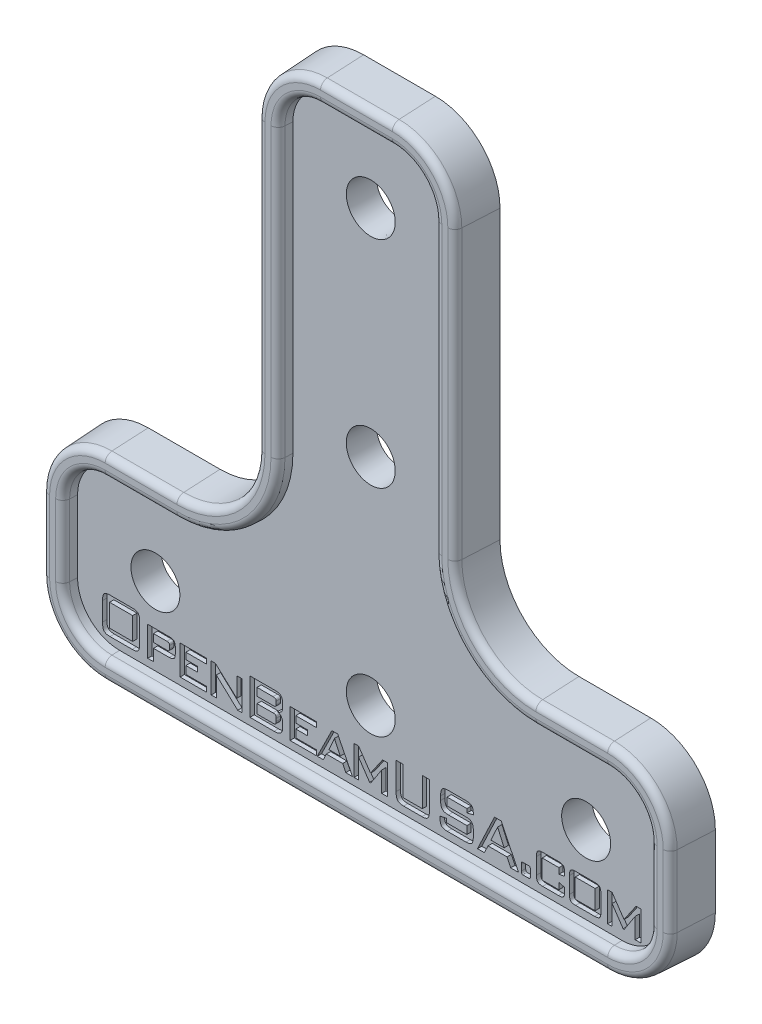
SolidWorks part; units mm, degrees
ref_plane "Front Plane" through (0, 0, 0) normal (0, 0, 1) x (1, 0, 0)
ref_plane "Top Plane" through (0, 0, 0) normal (0, 1, 0) x (1, 0, 0)
ref_plane "Right Plane" through (0, 0, 0) normal (1, 0, 0) x (0, 0, -1)
sketch "Sketch1" plane through (0, 0, 0) normal (0, 0, 1) x (1, 0, 0)
  line L0 (55, 0) -> (-55, 0) construction
  line L1 (-7.5, 30) -> (7.5, 30)
  line L2 (-7.5, 30) -> (-7.5, 0)
  line L3 (7.5, 0) -> (22.5, 0)
  line L4 (7.5, 30) -> (7.5, 0)
  line L5 (-22.5, 0) -> (-7.5, 0)
  line L6 (-22.5, 0) -> (-22.5, -15)
  line L7 (-22.5, -15) -> (22.5, -15)
  line L8 (22.5, 0) -> (22.5, -15)
  line L9 (0, 49.321) -> (0, -31.3726) construction
  line L10 (0, -54.6431) -> (0, 54.6431) construction
  dimension "D1" = 15
  dimension "D2" = 45
  dimension "D3" = 45
extrude "Boss-Extrude1" add sketch "Sketch1" along normal blind 2
fillet "Fillet1" radius 5 8 edges at (22.5, -15, 1) (22.5, 0, 1) (-7.5, 0, 1) (7.5, 0, 1) (7.5, 30, 1) (-22.5, -15, 1) (-22.5, 0, 1) (-7.5, 30, 1)
sketch "Sketch2" plane through (0, 0, 2) normal (0, 0, 1) x (1, 0, 0)
  line L0 (-22.5, -7.5) -> (22.5, -7.5) construction
  line L1 (-22.5, -5) -> (-22.5, -10) construction
  line L2 (22.5, -10) -> (22.5, -5) construction
  line L3 (0, 30) -> (0, -15) construction
  line L4 (2.5, 30) -> (-2.5, 30) construction
  line L5 (-17.5, -15) -> (17.5, -15) construction
  circle A0 centre (-15, -7.5) radius 1.6
  circle A1 centre (0, -7.5) radius 1.6
  circle A2 centre (15, -7.5) radius 1.6
  circle A3 centre (0, 22.5) radius 1.6
  circle A4 centre (0, 7.5) radius 1.6
  dimension "D1" = 3.2
  dimension "D2" = 15
  dimension "D3" = 15
  dimension "D4" = 15
  dimension "D5" = 15
extrude "Cut-Extrude1" cut sketch "Sketch2" against normal through all
other "Move Face1" flip direction yes face at (-9.4822, 1.9822, 1) face at (-15, 0, 1) face at (-20.5178, -1.9822, 1) face at (-22.5, -7.5, 1) face at (-20.5178, -13.0178, 1) face at (0, -15, 1) face at (20.5178, -13.0178, 1) face at (22.5, -7.5, 1) face at (20.5178, -1.9822, 1) face at (15, 0, 1) face at (9.4822, 1.9822, 1) face at (7.5, 15, 1) face at (5.5178, 28.0178, 1) face at (0, 30, 1) face at (-5.5178, 28.0178, 1) face at (-7.5, 15, 1) offset 0.5 parameters "D1"=0.5
draft "Draft1" type of draft neutral plane draft angle 3 faces to draft 21 face at (16.6, -7.5, 0) face at (1.6, 22.5, 0) face at (1.6, 7.5, 0) face at (1.6, -7.5, 0) face at (-13.4, -7.5, 0) face at (-20.216, -2.284, 1) face at (-22, -7.5, 1) face at (-20.216, -12.716, 1) face at (0, -14.5, 1) face at (20.216, -12.716, 1) face at (22, -7.5, 1) face at (20.216, -2.284, 1) face at (15, -0.5, 1) face at (9.1805, 1.6805, 1) face at (7, 15, 1) face at (5.216, 27.716, 1) face at (0, 29.5, 1) face at (-5.216, 27.716, 1) face at (-7, 15, 1) face at (-9.1805, 1.6805, 1) face at (-15, -0.5, 1) neutral plane through (0, 0, 0) neutral plane normal (0, 0, -1) reverse direction yes parameters "D1"=3
sketch "Sketch4" plane through (0, 0, 2) normal (0, 0, 1) x (1, 0, 0)
  line L0 (-17.5, -12.9214) -> (17.5, -12.9214)
  line L1 (20.4214, -10) -> (20.4214, -5)
  line L2 (17.5, -2.0786) -> (12.5, -2.0786)
  line L3 (5.4214, 5) -> (5.4214, 25)
  line L4 (2.5, 27.9214) -> (-2.5, 27.9214)
  line L5 (-5.4214, 25) -> (-5.4214, 5)
  line L6 (-12.5, -2.0786) -> (-17.5, -2.0786)
  line L7 (-20.4214, -5) -> (-20.4214, -10)
  line L8 (-17.5, -14.3952) -> (17.5, -14.3952)
  line L9 (21.8952, -10) -> (21.8952, -5)
  line L10 (17.5, -0.6048) -> (12.5, -0.6048)
  line L11 (6.8952, 5) -> (6.8952, 25)
  line L12 (2.5, 29.3952) -> (-2.5, 29.3952)
  line L13 (-6.8952, 25) -> (-6.8952, 5)
  line L14 (-12.5, -0.6048) -> (-17.5, -0.6048)
  line L15 (-21.8952, -5) -> (-21.8952, -10)
  line L16 (-17.5, -14.3952) -> (17.5, -14.3952)
  line L17 (21.8952, -10) -> (21.8952, -5)
  line L18 (17.5, -0.6048) -> (12.5, -0.6048)
  line L19 (6.8952, 5) -> (6.8952, 25)
  line L20 (2.5, 29.3952) -> (-2.5, 29.3952)
  line L21 (-6.8952, 25) -> (-6.8952, 5)
  line L22 (-12.5, -0.6048) -> (-17.5, -0.6048)
  line L23 (-21.8952, -5) -> (-21.8952, -10)
  arc A2 (17.5, -12.9214) -> (20.4214, -10) centre (17.5, -10) ccw
  arc A3 (20.4214, -5) -> (17.5, -2.0786) centre (17.5, -5) ccw
  arc A4 (5.4214, 5) -> (12.5, -2.0786) centre (12.5, 5) ccw
  arc A5 (5.4214, 25) -> (2.5, 27.9214) centre (2.5, 25) ccw
  arc A6 (-2.5, 27.9214) -> (-5.4214, 25) centre (-2.5, 25) ccw
  arc A7 (-12.5, -2.0786) -> (-5.4214, 5) centre (-12.5, 5) ccw
  arc A8 (-17.5, -2.0786) -> (-20.4214, -5) centre (-17.5, -5) ccw
  arc A9 (-20.4214, -10) -> (-17.5, -12.9214) centre (-17.5, -10) ccw
  arc A10 (17.5, -14.3952) -> (21.8952, -10) centre (17.5, -10) ccw
  arc A11 (21.8952, -5) -> (17.5, -0.6048) centre (17.5, -5) ccw
  arc A12 (6.8952, 5) -> (12.5, -0.6048) centre (12.5, 5) ccw
  arc A13 (6.8952, 25) -> (2.5, 29.3952) centre (2.5, 25) ccw
  arc A14 (-2.5, 29.3952) -> (-6.8952, 25) centre (-2.5, 25) ccw
  arc A15 (-12.5, -0.6048) -> (-6.8952, 5) centre (-12.5, 5) ccw
  arc A16 (-17.5, -0.6048) -> (-21.8952, -5) centre (-17.5, -5) ccw
  arc A17 (-21.8952, -10) -> (-17.5, -14.3952) centre (-17.5, -10) ccw
  arc A18 (17.5, -14.3952) -> (21.8952, -10) centre (17.5, -10) ccw
  arc A19 (21.8952, -5) -> (17.5, -0.6048) centre (17.5, -5) ccw
  arc A20 (6.8952, 5) -> (12.5, -0.6048) centre (12.5, 5) ccw
  arc A21 (6.8952, 25) -> (2.5, 29.3952) centre (2.5, 25) ccw
  arc A22 (-2.5, 29.3952) -> (-6.8952, 25) centre (-2.5, 25) ccw
  arc A23 (-12.5, -0.6048) -> (-6.8952, 5) centre (-12.5, 5) ccw
  arc A24 (-17.5, -0.6048) -> (-21.8952, -5) centre (-17.5, -5) ccw
  arc A25 (-21.8952, -10) -> (-17.5, -14.3952) centre (-17.5, -10) ccw
  dimension "D1" = 0
extrude "Boss-Extrude3" add sketch "Sketch4" along normal blind 1 draft 3
fillet "Fillet3" radius 0.5 32 edges at (-7.5317, 0.0317, 3) (-5.4738, 15, 3) (-4.6028, 27.1028, 3) (0, 27.9738, 3) (4.6028, 27.1028, 3) (5.4738, 15, 3) (7.5317, 0.0317, 3) (15, -2.0262, 3) (19.6028, -2.8972, 3) (20.4738, -7.5, 3) (19.6028, -12.1028, 3) (0, -12.9738, 3) (-19.6028, -12.1028, 3) (-20.4738, -7.5, 3) (-19.6028, -2.8972, 3) (-8.4997, 0.9997, 3) (-6.8428, 15, 3) (-5.5708, 28.0708, 3) (0, 29.3428, 3) (5.5708, 28.0708, 3) (6.8428, 15, 3) (8.4997, 0.9997, 3) (15, -0.6572, 3) (20.5708, -1.9292, 3) (21.8428, -7.5, 3) (20.5708, -13.0708, 3) (0, -14.3428, 3) (-20.5708, -13.0708, 3) (-21.8428, -7.5, 3) (-20.5708, -1.9292, 3) (-15, -2.0262, 3) (-15, -0.6572, 3)
sketch "Sketch5" plane through (0, 0, 0) normal (0, 0, -1) x (-1, 0, 0)
  line L0 (0, 54.6431) -> (0, -54.6431) construction
  line L1 (-14.5, -13.8) -> (14.5, -13.8)
  line L2 (-15, -13.3) -> (-15, -10.3)
  line L3 (-14.5, -9.8) -> (14.5, -9.8)
  line L4 (15, -13.3) -> (15, -10.3)
  line L5 (-15, -13.8) -> (15, -9.8) construction
  line L6 (-15, -9.8) -> (15, -13.8) construction
  line L7 (17.5, -14.5) -> (-17.5, -14.5) construction
  arc A0 (14.5, -13.8) -> (15, -13.3) centre (14.5, -13.3) ccw
  arc A1 (14.5, -9.8) -> (15, -10.3) centre (14.5, -10.3) cw
  arc A2 (-14.5, -13.8) -> (-15, -13.3) centre (-14.5, -13.3) cw
  arc A3 (-15, -10.3) -> (-14.5, -9.8) centre (-14.5, -10.3) cw
  point P0 (0, -11.8)
  dimension "D4" = 0.5
  dimension "D1" = 30
  dimension "D2" = 4
  dimension "D3" = 0.7
extrude "Cut-Extrude2" cut sketch "Sketch5" against normal blind 0.2 draft 3
sketch "Sketch6" plane through (0, 0, 2) normal (0, 0, 1) x (1, 0, 0)
  line L0 (-19.1832, -12.4214) -> (19.1832, -12.4214) construction
  line L3 (-17.5, -12.9214) -> (17.5, -12.9214) construction
  arc A0 (17.5, -12.949) -> (20.449, -10) centre (17.5, -10) ccw construction
  arc A1 (-20.449, -10) -> (-17.5, -12.949) centre (-17.5, -10) ccw construction
  text T0 "OpenBeamUSA.com" font "BankGothic Md BT" height 2.5
  dimension "D1" = 0.5
extrude "Cut-Extrude3" cut sketch "Sketch6" against normal blind 0.3
sketch "Sketch7" plane through (0, 0, 0) normal (0, 0, -1) x (-1, 0, 0)
  line L0 (-14.9895, -11.8) -> (14.9895, -11.8) construction
  line L2 (14.9895, -13.3) -> (14.9895, -10.3) construction
  text T0 "TL625-000101-002\r\n" font "Arial Narrow" height 1.5
  text T1 ">>PA66 + 30GF <<" font "Arial Narrow" height 1
split line "Split Line1"
sketch "Alignment_Sketch" plane through (0, 0, 0) normal (0, 0, -1) x (-1, 0, 0)
  line L0 (0, 22.5) -> (0, -7.5) construction
  line L1 (-15, -7.5) -> (15, -7.5) construction
  point P0 (-15, -7.5)
  point P1 (0, -7.5)
  point P3 (15, -7.5)
  point P5 (0, 7.5)
  point P7 (0, 22.5)
